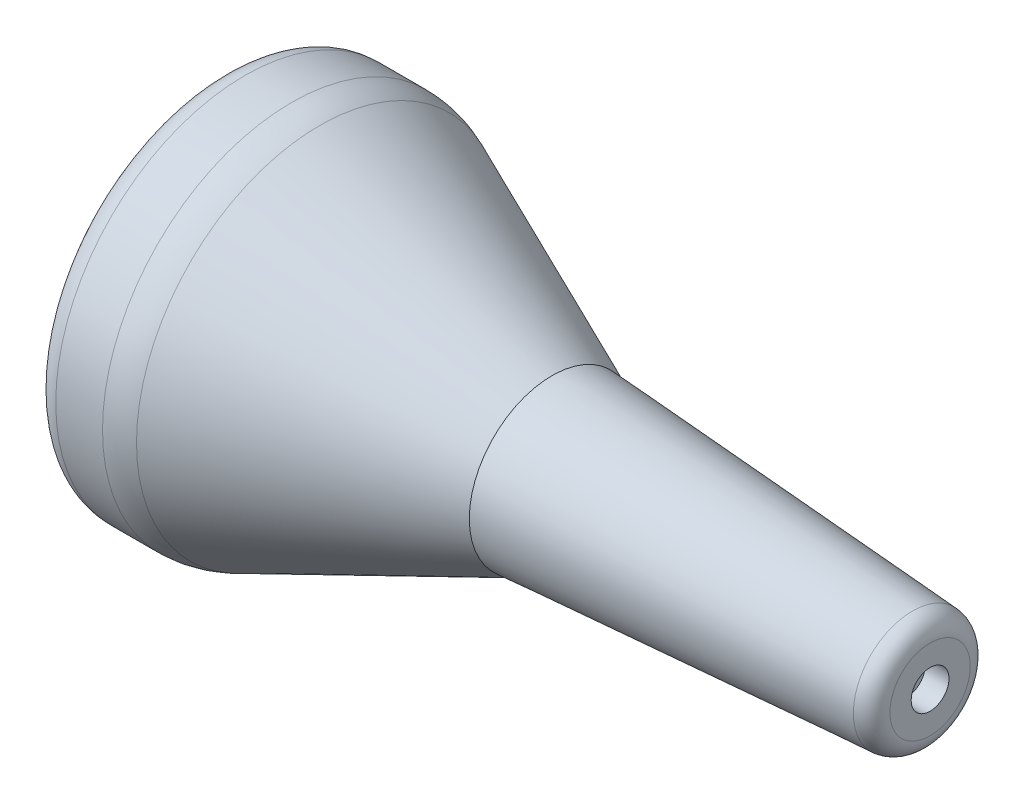
SolidWorks part; units mm, degrees
ref_plane "前视" through (0, 0, 0) normal (0, 0, 1) x (1, 0, 0)
ref_plane "上视" through (0, 0, 0) normal (0, 1, 0) x (1, 0, 0)
ref_plane "右视" through (0, 0, 0) normal (1, 0, 0) x (0, 0, -1)
sketch "草图1" plane through (0, 0, 0) normal (0, 0, 1) x (1, 0, 0)
  line L0 (0, 0) -> (0, 7)
  line L1 (1, 8) -> (2.9788, 8)
  line L2 (4.1701, 7.7533) -> (14, 3.5)
  line L3 (14, 3.5) -> (29.2524, 2.4991)
  line L4 (30, 1.7008) -> (30, 0.8)
  line L5 (30, 0.8) -> (29, 0.8)
  line L6 (29, 0.8) -> (29, 0)
  line L7 (29, 0) -> (0, 0)
  line L8 (30, 0) -> (0, 0) construction
  arc A0 (0, 7) -> (1, 8) centre (1, 7) cw
  arc A1 (2.9788, 8) -> (4.1701, 7.7533) centre (2.9788, 5) cw
  arc A2 (29.2524, 2.4991) -> (30, 1.7008) centre (29.2, 1.7008) cw
revolve "旋转1" add sketch "草图1" angle 360 about L8 reverse direction yes
ref_plane "基准面1" through (0, 0, 0) normal (0, 0, 1) x (1, 0, 0)
sketch "草图2" plane through (0, 0, 0) normal (0, 0, 1) x (1, 0, 0)
  line L0 (8.9865, 0) -> (-3.5865, 0)
  line L1 (50, 0) -> (-50, 0) construction
  arc A0 (-3.5865, 0) -> (8.9865, 0) centre (2.7, 0) cw
revolve "切除-旋转1" cut sketch "草图2" angle 360 about L1 reverse direction yes
ref_plane "基准面2" through (0, 0, 0) normal (0, 0, 1) x (1, 0, 0)
ref_plane "to_dummy XY" through (0, 0, 0) normal (0, 0, 1) x (1, 0, 0)
ref_plane "to_dummy XZ" through (0, 0, 0) normal (0, -1, 0) x (-1, 0, 0)
ref_plane "to_dummy YZ" through (2.7, 0, 0) normal (1, 0, 0) x (0, 0, -1)
ref_axis "to_dummy X" through (-80.9, 0, 0) along (1, 0, 0)
ref_axis "to_dummy Y" through (2.7, -50, 0) along (0, 1, 0)
ref_axis "to_dummy Z" through (2.7, 0, 80.9) along (0, 0, -1)
sketch3d "to_dummy"
  point P0 (2.7, 0, 0)
